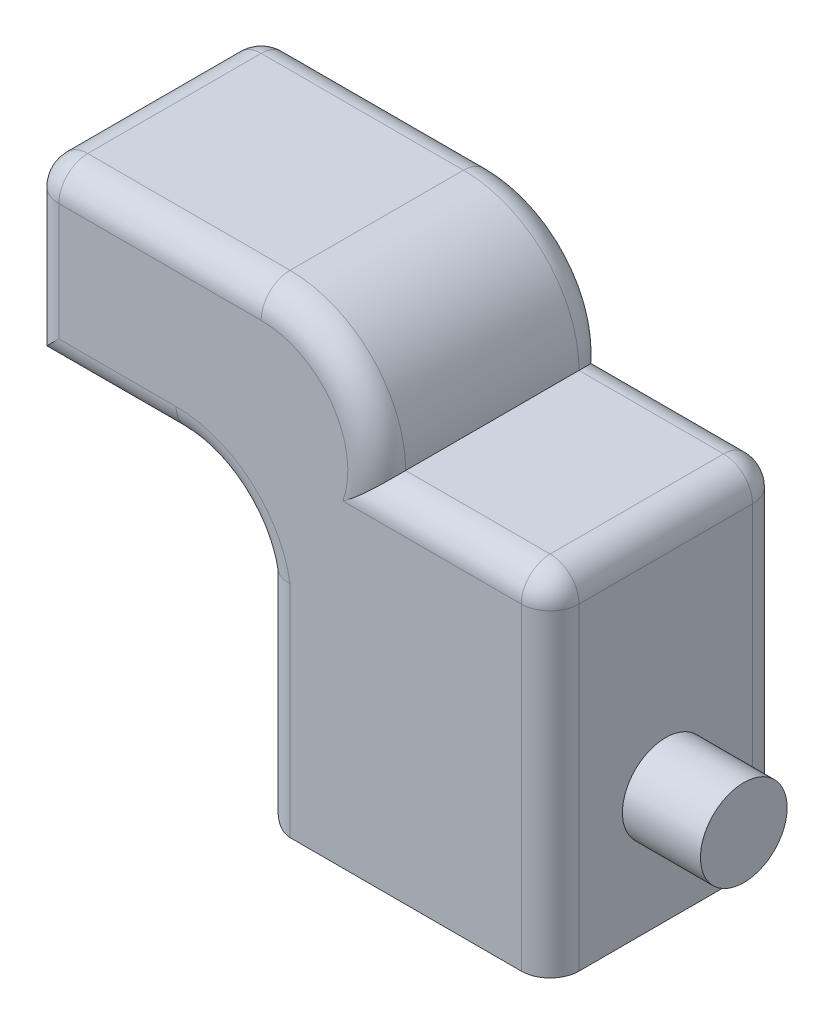
SolidWorks part; units mm, degrees
ref_plane "Front Plane" through (0, 0, 0) normal (0, 0, 1) x (1, 0, 0)
ref_plane "Top Plane" through (0, 0, 0) normal (0, 1, 0) x (1, 0, 0)
ref_plane "Right Plane" through (0, 0, 0) normal (1, 0, 0) x (0, 0, -1)
sketch "Sketch1" plane through (0, 0, 0) normal (0, 0, 1) x (1, 0, 0)
  line L0 (33.538, 40.64) -> (53.858, 40.64)
  line L1 (64.018, 30.48) -> (76.718, 30.48)
  line L2 (79.258, 27.94) -> (79.258, 0)
  line L3 (79.258, 0) -> (24.2797, 0)
  line L4 (33.538, 25.2611) -> (46.3823, 25.2611)
  line L5 (33.538, 40.64) -> (33.538, 25.2611)
  line L6 (53.858, 19.1168) -> (53.858, 0)
  line L7 (53.858, 0) -> (24.2797, 0)
  arc A0 (53.858, 40.64) -> (64.018, 30.48) centre (53.858, 30.48) cw
  arc A1 (46.3823, 25.2611) -> (53.858, 19.1168) centre (46.3823, 17.6411) cw
  arc A2 (76.718, 30.48) -> (79.258, 27.94) centre (76.718, 27.94) cw
  point P15 (79.258, 30.48)
  dimension "D4" = 7.62
  dimension "D3" = 10.16
  dimension "D5" = 2.54
  dimension "D1" = 30.48
  dimension "D2" = 20.32
  dimension "D6" = 12.7
extrude "Boss-Extrude1" add sketch "Sketch1" along normal blind 20.32 contours A2 L1 A0 L0 L5 L4 A1 L6 L3 L2 region at (59.7609, 21.3498, 0)
sketch "Sketch2" plane through (79.258, 0, 0) normal (1, 0, 0) x (0, 0, -1)
  line L0 (-20.32, 0) -> (0, 0) construction
  line L1 (-10.16, 0) -> (-10.16, 27.94) construction
  line L2 (-20.32, 27.94) -> (0, 27.94) construction
  circle A0 centre (-10.16, 10.16) radius 3.81
  dimension "D1" = 7.62
  dimension "D2" = 10.16
extrude "Boss-Extrude2" add sketch "Sketch2" along normal blind 6.858
fillet "Fillet1" radius 2.54 21 edges at (78.5141, 29.7361, 0) (78.5141, 29.7361, 20.32) (61.0422, 37.6642, 0) (61.0422, 37.6642, 20.32) (51.2206, 23.5279, 0) (51.2206, 23.5279, 20.32) (66.558, 0, 0) (79.258, 13.97, 0) (70.368, 30.48, 0) (79.258, 13.97, 20.32) (70.368, 30.48, 20.32) (43.698, 40.64, 0) (33.538, 40.64, 10.16) (33.538, 32.9505, 0) (33.538, 32.9505, 20.32) (43.698, 40.64, 20.32) (53.858, 0, 10.16) (39.9601, 25.2611, 0) (39.9601, 25.2611, 20.32) (53.858, 9.5584, 0) (53.858, 9.5584, 20.32)
